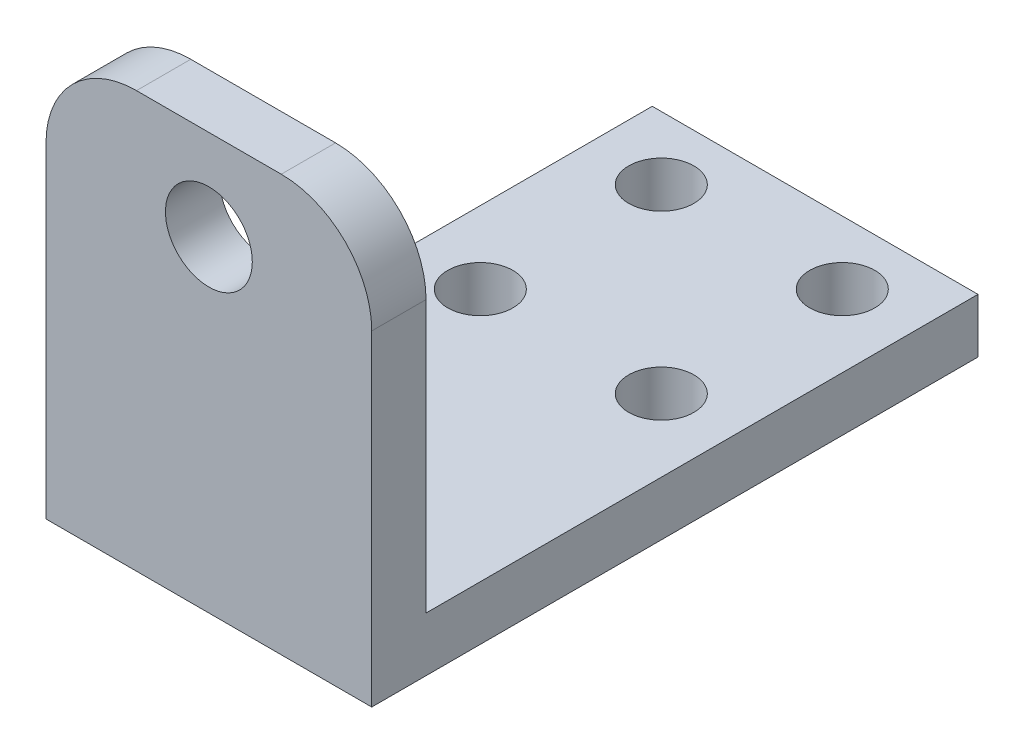
SolidWorks part; units mm, degrees
ref_plane "Front Plane" through (0, 0, 0) normal (0, 0, 1) x (1, 0, 0)
ref_plane "Top Plane" through (0, 0, 0) normal (0, 1, 0) x (1, 0, 0)
ref_plane "Right Plane" through (0, 0, 0) normal (1, 0, 0) x (0, 0, -1)
sketch "Sketch1" plane through (0, 0, 0) normal (1, 0, 0) x (0, 0, -1)
  line L0 (0, 0) -> (33.5, 0)
  line L1 (33.5, 0) -> (33.5, 3)
  line L2 (33.5, 3) -> (3, 3)
  line L3 (3, 3) -> (3, 23)
  line L4 (3, 23) -> (0, 23)
  line L5 (0, 23) -> (0, 0)
  point P2 (4.7435, 5.4647)
  point P7 (0, 0)
  point P8 (3.5844, 1.4077)
  dimension "D1" = 3
  dimension "D2" = 23
  dimension "D3" = 33.5
extrude "Boss-Extrude1" add sketch "Sketch1" along normal blind 18
sketch "Sketch2" plane through (0, 0, 0) normal (0, 0, 1) x (1, 0, 0)
  line L0 (0, 0) -> (18, 0) construction
  line L2 (9, 0) -> (9, 18) construction
  line L3 (18, 23) -> (0, 23) construction
  point P7 (9, 18)
  point P13 (9, 18)
  dimension "D1" = 5
hole_wizard "M4 Clearance Hole1" positions "Sketch2" profile "Sketch3" hole size "M4" standard "ANSI Metric"
sketch "Sketch3" plane through (9, 18, 0) normal (1, 0, 0) x (0, -1, 0)
  line L0 (0, 0) -> (0, 4.4421)
  line L1 (0, 4.4421) -> (2.4, 3)
  line L2 (2.4, 3) -> (2.4, 0)
  line L5 (2.4, 0) -> (0, 0)
  line L10 (0, 4.4421) -> (-2.4, 3) construction
  line L11 (0, -6.35) -> (0, 107.95) construction
  dimension "Hole Dia." = 4.8
  dimension "Hole Depth" = 3
  dimension "Drill Angle" = 118
fillet "Fillet1" radius 5 2 edges at (0, 23, -1.5) (18, 23, -1.5)
sketch "Sketch4" plane through (0, 3, 0) normal (0, 1, 0) x (1, 0, 0)
  line L0 (9, 33.5) -> (9, 3) construction
  line L1 (18, 33.5) -> (0, 33.5) construction
  line L2 (18, 3) -> (0, 3) construction
  line L4 (18, 25) -> (0, 25) construction
  line L7 (0, 33.5) -> (0, 3) construction
  line L8 (18, 33.5) -> (18, 3) construction
  point P42 (4, 30)
  point P45 (4, 20)
  point P46 (14, 20)
  point P47 (14, 30)
  point P48 (18, 18.25)
  point P51 (0, 0)
  point P52 (0, 0)
  point P53 (0, 25)
  point P56 (18, 25)
  dimension "D1" = 5
  dimension "D2" = 5
  dimension "D3" = 8.5
hole_wizard "M3 Clearance Hole1" positions "Sketch4" profile "Sketch5" hole size "M3" standard "ANSI Metric" end condition through all
sketch "Sketch5" plane through (14, 3, -30) normal (1, 0, 0) x (0, 0, 1)
  line L0 (0, 0) -> (0, 3)
  line L1 (0, 3) -> (1.8, 3)
  line L2 (1.8, 3) -> (1.8, 0)
  line L5 (1.8, 0) -> (0, 0)
  line L11 (0, -6.35) -> (0, 107.95) construction
  dimension "Thru Hole Dia." = 3.6
  dimension "Thru Hole Depth" = 3
